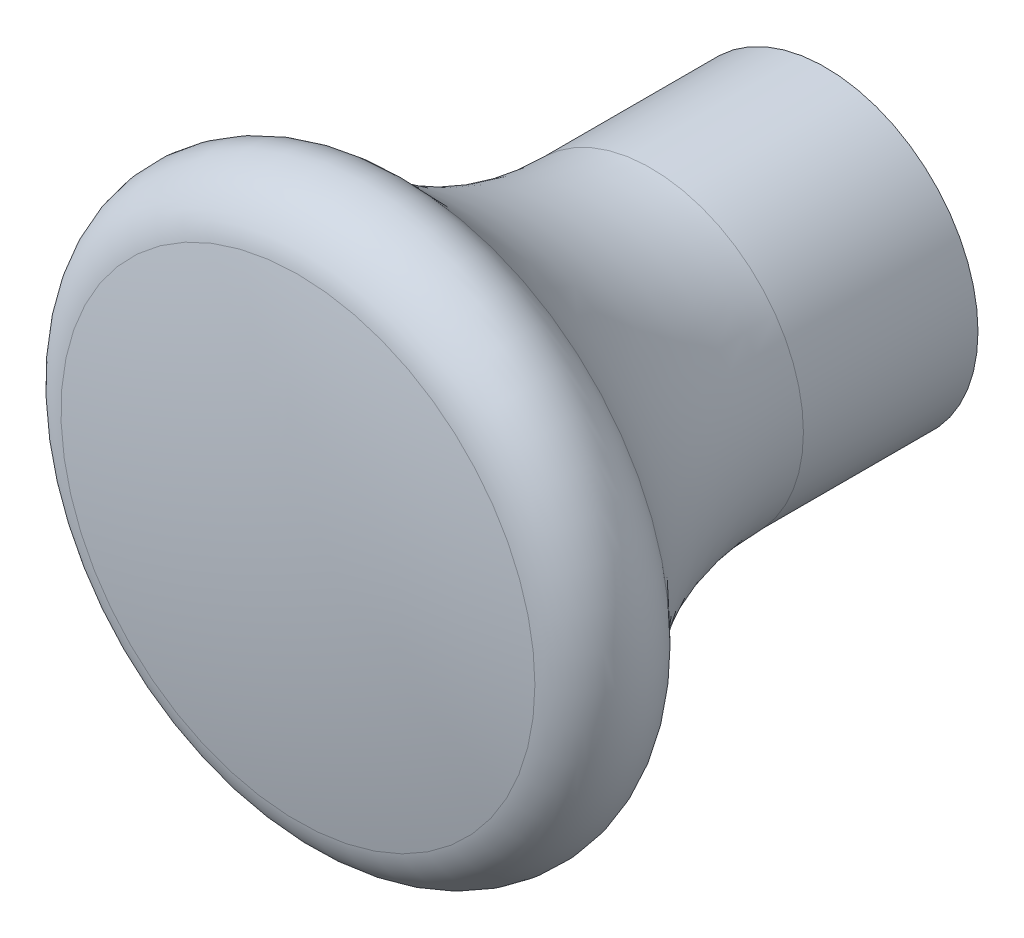
SolidWorks part; units mm, degrees
material "AISI 316 Annealed Stainless Steel Bar (SS)"
ref_plane "Front" through (0, 0, 0) normal (0, 0, 1) x (1, 0, 0)
ref_plane "Top" through (0, 0, 0) normal (0, 1, 0) x (1, 0, 0)
ref_plane "Right" through (0, 0, 0) normal (1, 0, 0) x (0, 0, -1)
sketch "Sketch1" plane through (0, 0, 0) normal (1, 0, 0) x (0, 0, -1)
  line L0 (0, 0) -> (0, 5.9531)
  line L1 (0, 5.9531) -> (-6.8118, 5.9531)
  line L2 (-21.4312, 0) -> (0, 0)
  line L3 (-18.8621, 11.1125) -> (2.9755, 11.1125) construction
  line L4 (-21.4312, 0) -> (-21.4312, -15.5662) construction
  arc A0 (-6.8118, 5.9531) -> (-16.4364, 10.3673) centre (-6.8118, 18.6531) cw
  arc A1 (-16.4364, 10.3673) -> (-20.5825, 9.2471) centre (-18.2411, 8.8137) ccw
  arc A2 (-20.5825, 9.2471) -> (-21.4312, 0) centre (29.3687, 0) ccw
  dimension "D3" = 12.7
  dimension "D4" = 2.3813
  dimension "D5" = 50.8
  dimension "D1" = 5.9531
  dimension "D2" = 21.4312
  dimension "D6" = 11.1125
revolve "Revolve1" add sketch "Sketch1" angle 360 about L2
hole_wizard "1/4-20 Tapped Hole1" positions "Sketch2" profile "Sketch3" tap size "1/4-20" standard "ANSI Inch"
sketch "Sketch2" plane through (0, 0, 0) normal (0, 0, -1) x (-1, 0, 0)
  point P0 (0, 0)
sketch "Sketch3" plane through (0, 0, 0) normal (1, 0, 0) x (0, 1, 0)
  line L0 (0, 0) -> (0, 18.0438)
  line L1 (0, 18.0438) -> (2.5527, 16.51)
  line L2 (2.5527, 16.51) -> (2.5527, 0)
  line L5 (2.5527, 0) -> (0, 0)
  line L10 (0, 18.0438) -> (-2.5527, 16.51) construction
  line L11 (0, -6.35) -> (0, 107.95) construction
  dimension "Tap Drill Dia." = 5.1054
  dimension "Tap Drill Depth" = 16.51
  dimension "Drill Angle" = 118
thread "Thread1" pitch 1.27 method cut profile "Thread Profile1" start angle 0, offset 1, length 12.7, pitch 1.27, diameter 5.1054
ref_plane "Plane1" through (2.5527, 0, -1) normal (0, -1, 0) x (1, 0, 0)
sketch "Thread Profile1" plane through (2.5527, 0, -1) normal (0, -1, 0) x (1, 0, 0)
  line L0 (0, 0) -> (0, 1.27) construction
  line L1 (0, 0) -> (0.6874, 0.3969)
  line L2 (0.6874, 0.3969) -> (0.6874, 0.5556)
  line L3 (0.6874, 0.5556) -> (0, 0.9525)
  line L4 (0.6874, 0.4762) -> (0, 0.4762) construction
  line L11 (0, 0) -> (0, 0.9525)
  point P2 (0, 0)
  dimension "Pitch" = 1.27
  dimension "Profile_Angle" = 60
  dimension "Profile_Land" = 0.1588
  dimension "Profile_Height" = 0.6874
